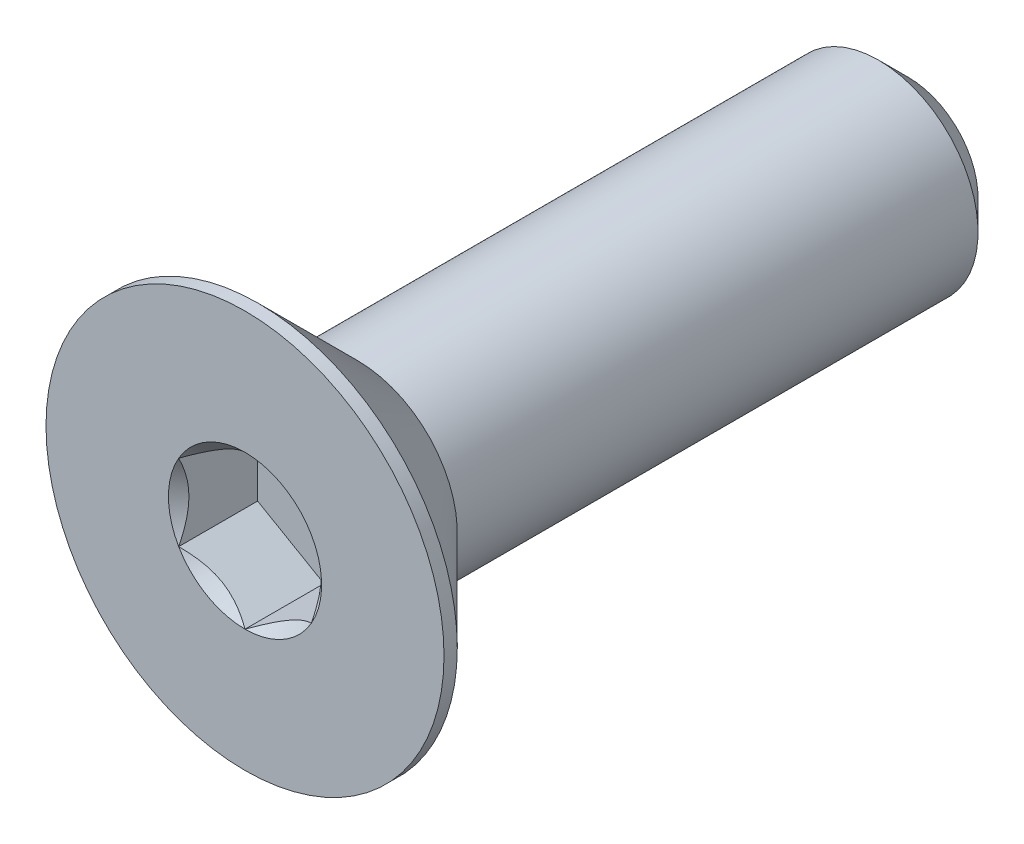
SolidWorks part; units mm, degrees
material "Alloy Steel"
ref_plane "Front" through (0, 0, 0) normal (0, 0, 1) x (1, 0, 0)
ref_plane "Top" through (0, 0, 0) normal (0, 1, 0) x (1, 0, 0)
ref_plane "Right" through (0, 0, 0) normal (1, 0, 0) x (0, 0, -1)
sketch "Sketch1" plane through (0, 0, 0) normal (1, 0, 0) x (0, 0, -1)
  line L0 (-5, 3) -> (-4.8, 3) construction
  line L1 (-4.8, 3) -> (-3.3, 1.5) construction
  line L2 (-5, 1.5) -> (5, 1.5) construction
  line L3 (5, 1.5) -> (5, 0) construction
  line L4 (5, 0) -> (-5, 0) construction
  line L5 (-5, 0) -> (-5, 3) construction
  line L6 (-5, 3) -> (-5, -3) construction
  line L7 (5, 1.5) -> (5, -1.5) construction
  line L8 (-5, -3) -> (-4.8, -3) construction
  line L9 (-4.8, -3) -> (-3.3, -1.5) construction
  line L11 (-5, 1.5) -> (-5, 0) construction
  line L12 (-3.3, 1.5) -> (-3.3, 0) construction
  line L13 (4.9687, 1.5541) -> (5.2187, 1.1211) construction
  line L14 (5.2187, 1.1211) -> (5.4688, 1.5541) construction
  line L15 (5.4688, 1.5541) -> (4.9687, 1.5541) construction
  line L16 (5.2187, 1.5541) -> (5.2187, 1.5) construction
  line L17 (5.2187, 1.5) -> (5.2187, 1.1752) construction
  line L18 (5.2187, 1.1752) -> (5.2187, 1.1211) construction
  line L19 (5.2187, 1.5271) -> (5.4531, 1.5271) construction
  line L20 (5.2187, 1.5271) -> (4.9844, 1.5271) construction
  line L21 (5, 1.5) -> (5.4375, 1.5) construction
  line L22 (5.1875, 1.1752) -> (5.25, 1.1752) construction
  line L23 (5, -1.5) -> (-3.3, -1.5) construction
  point P10 (3.75, -1.5)
  point P24 (-3.3, 1.5)
  point P30 (0, 0)
  dimension "Head Diameter" = 6
  dimension "Head Height" = 1.7
  dimension "Length" = 10
  dimension "Countersink Angle" = 90
  dimension "Thread Pitch" = 0.5
  dimension "D2" = 0.0625
  dimension "Minimum Thread Length" = 8.3
  dimension "Thread Size" = 3
  dimension "D1" = 1.25
sketch "Sketch2" plane through (0, 0, 0) normal (0, 0, 1) x (1, 0, 0)
  line L1 (0, 1.1547) -> (-1, 0.5774) construction
  line L2 (-1, 0.5774) -> (-1, -0.5774) construction
  line L3 (-1, -0.5774) -> (0, -1.1547) construction
  line L4 (0, -1.1547) -> (1, -0.5774) construction
  line L5 (1, -0.5774) -> (1, 0.5774) construction
  line L6 (1, 0.5774) -> (0, 1.1547) construction
  circle A0 centre (0, 0) radius 1 construction
  dimension "Drive Size" = 2
sketch "Sketch3" plane through (0, 0, 0) normal (1, 0, 0) x (0, 0, -1)
  line L0 (-5, 1.5) -> (5, 1.5)
  line L1 (5, 1.5) -> (5, 0)
  line L2 (5, 0) -> (-5, 0)
  line L3 (-5, 0) -> (-5, 1.5)
revolve "Revolve1" add sketch "Sketch3" angle 360 about L4
chamfer "Chamfer1" distance 0.45 angle 45 1 edges at (0, 1.5, -5)
sketch "Sketch6" plane through (0, 0, 0) normal (1, 0, 0) x (0, 0, -1)
  line L0 (-5, 3) -> (-4.8, 3)
  line L1 (-4.8, 3) -> (-3.3, 1.5)
  line L2 (-3.3, 1.5) -> (-3.3, 0)
  line L3 (-3.3, 0) -> (-5, 0)
  line L4 (-5, 0) -> (-5, 3)
revolve "Revolve2" add sketch "Sketch6" angle 360 about L4
sketch "Sketch8" plane through (0, 0, 5) normal (0, 0, 1) x (1, 0, 0)
  line L0 (0, 1.1547) -> (-1, 0.5774) construction
  line L1 (1, 0.5774) -> (0, 1.1547) construction
  line L2 (1, -0.5774) -> (1, 0.5774) construction
  line L3 (0, -1.1547) -> (1, -0.5774) construction
  line L4 (-1, 0.5774) -> (-1, -0.5774) construction
  line L5 (-1, -0.5774) -> (0, -1.1547) construction
  line L6 (0, 1.1547) -> (-1, 0.5774)
  line L7 (1, 0.5774) -> (0, 1.1547)
  line L8 (1, -0.5774) -> (1, 0.5774)
  line L9 (0, -1.1547) -> (1, -0.5774)
  line L10 (-1, 0.5774) -> (-1, -0.5774)
  line L11 (-1, -0.5774) -> (0, -1.1547)
extrude "Cut-Extrude1" cut sketch "Sketch8" against normal blind 1.19
sketch "Sketch9" plane through (0, 0, 5) normal (0, 0, 1) x (1, 0, 0)
  circle A0 centre (0, 0) radius 1.1547
extrude "Cut-Extrude2" cut sketch "Sketch9" against normal up to next (1.19 mm away) draft 45
ref_plane "Plane1" [suppressed] through (0, 0, 3.3) normal (0, 0, 1) x (1, 0, 0)
split "Split1" [suppressed] bodies to split 124
sketch "Sketch4" [suppressed] plane through (0, 0, -5) normal (0, 0, -1) x (-1, 0, 0)
  circle A0 centre (0, 0) radius 1.5 construction
  circle A1 centre (0, 0) radius 1.5
curve "Helix/Spiral1" [suppressed] pitch 0.5 height 8.8 turns 17.6
sketch "Sketch10" [suppressed] plane through (0, 0, 0) normal (1, 0, 0) x (0, 0, -1)
  line L0 (4.9844, 1.5271) -> (5.4531, 1.5271)
  line L1 (5.4531, 1.5271) -> (5.25, 1.1752)
  line L2 (5.25, 1.1752) -> (5.1875, 1.1752)
  line L3 (5.1875, 1.1752) -> (4.9844, 1.5271)
sweep "Cut-Sweep1" [suppressed] cut profiles "Sketch10" path "Helix/Spiral1"
equation "\"D2@Sketch1\" = \"Thread Pitch@Sketch1\" / 8"
equation "\"D4@Helix/Spiral1\"=\"Thread Pitch@Sketch1\""
equation "\"D3@Helix/Spiral1\"=\"Minimum Thread Length@Sketch1\"+\"Thread Pitch@Sketch1\""
equation "\"D1@Chamfer1\"=\"Thread Size@Sketch1\"*.15"
equation "\"D1@Cut-Extrude1\"=\"Head Height@Sketch1\"*.7"
equation "\"D1@Sketch1\"=\"Thread Pitch@Sketch1\"*2.5"
